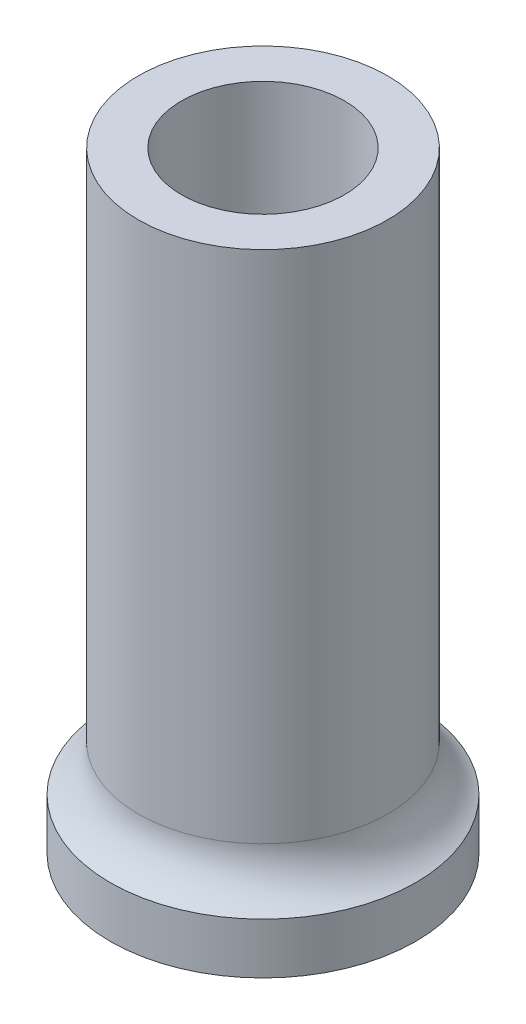
SolidWorks part; units mm, degrees
ref_plane "Front Plane" through (0, 0, 0) normal (0, 0, 1) x (1, 0, 0)
ref_plane "Top Plane" through (0, 0, 0) normal (0, 1, 0) x (1, 0, 0)
ref_plane "Right Plane" through (0, 0, 0) normal (1, 0, 0) x (0, 0, -1)
sketch "Sketch1" plane through (0, 0, 0) normal (0, 1, 0) x (1, 0, 0)
  circle A0 centre (0, 0) radius 1.5
  circle A1 centre (0, 0) radius 2.45
  dimension "D1" = 3
  dimension "D2" = 4.9
extrude "Boss-Extrude1" add sketch "Sketch1" along normal blind 11
sketch "Sketch2" plane through (0, 0, 0) normal (0, -1, 0) x (-1, 0, 0)
  circle A0 centre (0, 0) radius 3
  dimension "D1" = 6
extrude "Boss-Extrude2" add sketch "Sketch2" along normal blind 1
sketch "Sketch3" plane through (0, -1, 0) normal (0, -1, 0) x (-1, 0, 0)
  circle A0 centre (0, 0) radius 1.6
  dimension "D1" = 3.2
extrude "Cut-Extrude1" cut sketch "Sketch3" against normal through all
fillet "Fillet2" radius 1 1 edges at (0, 0, -2.45)
